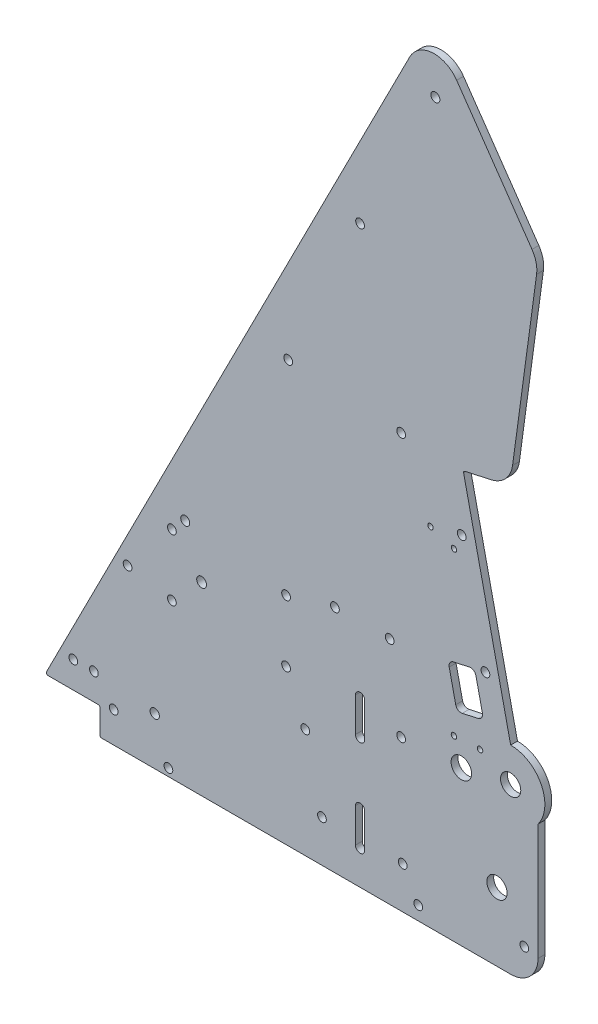
SolidWorks part; units mm, degrees
other "Markup1"
sketch "Sketch5"
ref_plane "Front Plane" through (0, 0, 0) normal (0, 0, 1) x (1, 0, 0)
ref_plane "Top Plane" through (0, 0, 0) normal (0, 1, 0) x (1, 0, 0)
ref_plane "Right Plane" through (0, 0, 0) normal (1, 0, 0) x (0, 0, -1)
sketch "Sketch1" plane through (0, 0, 0) normal (0, 0, 1) x (1, 0, 0)
  line L1 (228.6, -12.7) -> (228.6, 53.975)
  line L2 (178.7547, 351.4131) -> (0, 0)
  line L3 (228.6, 279.4) -> (178.7547, 351.4131)
  line L5 (0, 0) -> (25.4, 0)
  line L6 (25.4, 0) -> (25.4, -12.7)
  line L7 (25.4, -12.7) -> (228.6, -12.7)
  line L9 (215.9, 79.375) -> (193.9097, 178.5667)
  line L10 (193.9097, 178.5667) -> (215.6079, 183.377)
  line L11 (215.6079, 183.377) -> (228.6, 279.4)
  arc A0 (228.6, 53.975) -> (215.9, 79.375) centre (215.9, 63.5) ccw
  dimension "D7" = 12.7
  dimension "D8" = 76.2
  dimension "D10" = 31.75
  dimension "D2" = 292.1
  dimension "D3" = 25.4
  dimension "D4" = 215.9
  dimension "D5" = 394.2644
  dimension "D6" = 203.2
  dimension "D9" = 63.039
  dimension "D11" = 101.6
  dimension "D12" = 12.5
  dimension "D13" = 22.225
extrude "Boss-Extrude1" add sketch "Sketch1" along normal blind 3.175
sketch "Sketch2" plane through (0, 0, 3.175) normal (0, 0, 1) x (1, 0, 0)
  line L0 (178.7547, 351.4131) -> (0, 0) construction
  line L1 (25.4, -12.7) -> (228.6, -12.7) construction
  line L2 (215.9, 79.375) -> (193.9097, 178.5667) construction
  line L3 (193.9097, 178.5667) -> (215.6079, 183.377) construction
  line L4 (215.9, 79.375) -> (193.9097, 178.5667) construction
  line L5 (64.9432, 94.0578) -> (72.5445, 73.1732) construction
  line L6 (64.9432, 94.0578) -> (103.3734, 94.0578) construction
  line L10 (228.6, -12.7) -> (228.6, 53.975) construction
  circle A0 centre (64.9432, 94.0578) radius 2.0955
  circle A1 centre (180.975, 322.1643) radius 2.0955
  circle A2 centre (72.5445, 73.1732) radius 2.286
  circle A3 centre (193.2078, 152.3944) radius 2.032
  circle A4 centre (215.9, 63.5) radius 4.699
  circle A7 centre (173.0375, -6.35) radius 2.032
  circle A8 centre (204.203, 102.7985) radius 2.032
  circle A26 centre (209.55, 19.05) radius 4.699
  arc A30 (228.6, 53.975) -> (215.9, 79.375) centre (215.9, 63.5) ccw construction
  circle A31 centre (165.1, 179.3875) radius 2.032
  circle A35 centre (111.724, 87.4607) radius 2.032
  circle A36 centre (111.724, 58.8857) radius 2.032
  circle A37 centre (58.765, 58.8857) radius 2.032
  circle A38 centre (58.765, 87.4607) radius 2.032
  circle A39 centre (111.724, 58.8857) radius 1.905 construction
  circle A42 centre (111.724, 87.4607) radius 1.905 construction
  circle A43 centre (58.765, 58.8857) radius 1.905 construction
  circle A44 centre (58.765, 87.4607) radius 1.905 construction
  dimension "D3" = 4.191
  dimension "D5" = 4.191
  dimension "D9" = 4.572
  dimension "D20" = 9.398
  dimension "D23" = 9.398
  dimension "D18" = 4.064
  dimension "D26" = 4.064
  dimension "D14" = 4.064
  dimension "D10" = 4.064
  dimension "D2" = 15.24
  dimension "D6" = 15.24
  dimension "D7" = 22.225
  dimension "D21" = 44.45
  dimension "D22" = 6.35
  dimension "D19" = 160.3375
  dimension "D24" = 44.45
  dimension "D25" = 6.35
  dimension "D27" = 25.4
  dimension "D28" = 50.8
  dimension "D29" = 6.35
  dimension "D17" = 6.35
  dimension "D33" = 55.5625
  dimension "D15" = 114.3
  dimension "D4" = 180.975
  dimension "D8" = 70
extrude "Cut-Extrude1" cut sketch "Sketch2" against normal through all
sketch "Sketch7" plane through (0, 0, 3.175) normal (0, 0, 1) x (1, 0, 0)
  line L0 (146.05, 3.175) -> (146.05, 19.05) construction
  line L1 (143.891, 3.175) -> (143.891, 19.05)
  line L2 (148.209, 3.175) -> (148.209, 19.05)
  line L3 (146.05, 47.625) -> (146.05, 63.5) construction
  line L4 (143.891, 47.625) -> (143.891, 63.5)
  line L5 (148.209, 47.625) -> (148.209, 63.5)
  line L6 (25.4, -12.7) -> (228.6, -12.7) construction
  line L12 (228.6, -12.7) -> (228.6, 53.975) construction
  line L13 (25.4, -12.7) -> (228.6, -12.7) construction
  arc A0 (143.891, 3.175) -> (148.209, 3.175) centre (146.05, 3.175) ccw
  arc A1 (148.209, 19.05) -> (143.891, 19.05) centre (146.05, 19.05) ccw
  arc A2 (143.891, 47.625) -> (148.209, 47.625) centre (146.05, 47.625) ccw
  arc A3 (148.209, 63.5) -> (143.891, 63.5) centre (146.05, 63.5) ccw
  circle A8 centre (50.8, 9.525) radius 2.159
  point P2 (146.05, 11.1125)
  point P9 (146.05, 55.5625)
  dimension "D1" = 4.318
  dimension "D5" = 4.318
  dimension "D2" = 15.875
  dimension "D3" = 15.875
  dimension "D4" = 44.45
  dimension "D6" = 95.25
  dimension "D7" = 82.55
  dimension "D8" = 15.875
  dimension "D9" = 22.225
extrude "Cut-Extrude2" cut sketch "Sketch7" against normal through all
sketch "Sketch10" plane through (0, 0, 3.175) normal (0, 0, 1) x (1, 0, 0)
  circle A0 centre (120.65, 38.1) radius 2.032
  circle A1 centre (165.1, 57.15) radius 2.032
  circle A2 centre (13.0465, 12.3347) radius 2.032
  circle A3 centre (22.5715, 12.3347) radius 2.032
  circle A4 centre (38.2114, 62.6398) radius 2.032
  dimension "D1" = 4.064
  dimension "D3" = 38.1
  dimension "D2" = 120.65
  dimension "D4" = 63.5
  dimension "D5" = 69.85
extrude "Cut-Extrude3" cut sketch "Sketch10" against normal up to next
fillet "Fillet1" radius 12.7 4 edges at (228.6, -12.7, 1.5875) (178.7547, 351.4131, 1.5875) (215.6079, 183.377, 1.5875) (228.6, 279.4, 1.5875)
fillet "Fillet2" radius 0.7937 4 edges at (25.4, -12.7, 1.5875) (25.4, 0, 1.5875) (193.9097, 178.5667, 1.5875) (0, 0, 1.5875)
sketch "Sketch12" plane through (0, 0, 3.175) normal (0, 0, 1) x (1, 0, 0)
  circle A0 centre (31.75, 1.5875) radius 2.032
  circle A1 centre (173.0375, -6.35) radius 2.032
  circle A2 centre (222.25, 1.5875) radius 2.032
  circle A3 centre (57.15, -9.2075) radius 2.032
  circle A4 centre (57.15, -9.2075) radius 2.286 construction
  dimension "D1" = 4.064
  dimension "D2" = 4.064
extrude "Cut-Extrude5" cut sketch "Sketch12" against normal through all
sketch "Sketch13" plane through (0, 0, 3.175) normal (0, 0, 1) x (1, 0, 0)
  line L1 (228.6, 0) -> (228.6, 53.975) construction
  line L2 (1.2943, 0) -> (24.6062, 0) construction
  line L3 (26.1937, -12.7) -> (215.9, -12.7) construction
  circle A0 centre (112.7125, 182.5625) radius 2.032
  circle A1 centre (146.05, 254) radius 2.032
  dimension "D2" = 4.064
  dimension "D5" = 4.064
  dimension "D1" = 195.2625
  dimension "D3" = 82.55
  dimension "D4" = 254
  dimension "D6" = 115.8875
extrude "Cut-Extrude6" cut sketch "Sketch13" against normal through all
sketch "Sketch14" plane through (0, 0, 3.175) normal (0, 0, 1) x (1, 0, 0)
  line L5 (186.8444, 98.9502) -> (199.2434, 101.699)
  line L6 (186.8444, 98.9502) -> (190.9676, 80.3518)
  line L7 (190.9676, 80.3518) -> (203.3665, 83.1006)
  line L8 (199.2434, 101.699) -> (203.3665, 83.1006)
  line L14 (202.8168, 85.5804) -> (199.7931, 99.2192) construction
  line L15 (193.4474, 80.9015) -> (200.8868, 82.5508) construction
  line L16 (187.3942, 96.4704) -> (190.4178, 82.8316) construction
  line L17 (196.7636, 101.1493) -> (189.3242, 99.5) construction
  circle A0 centre (189.6022, 69.9806) radius 1.27
  circle A1 centre (201.7089, 70.5092) radius 1.27
  circle A2 centre (189.6022, 69.9806) radius 1.27 construction
  circle A3 centre (201.7089, 70.5092) radius 1.27 construction
  circle A4 centre (159.7935, 93.98) radius 2.032
  circle A5 centre (134.3935, 93.98) radius 2.032
  circle A6 centre (178.7216, 148.5324) radius 1.27
  circle A8 centre (178.7216, 148.5324) radius 1.27 construction
  circle A9 centre (189.6226, 145.0954) radius 1.27
  circle A10 centre (189.6226, 145.0954) radius 1.27 construction
  circle A11 centre (128.361, 6.6675) radius 2.032
  circle A12 centre (165.826, 6.6675) radius 2.032
  point P8 (152.4, 88.9)
  dimension "D1" = 4.064
extrude "Cut-Extrude7" cut sketch "Sketch14" against normal through all both and the other way through all
fillet "Fillet3" radius 2.54 4 edges at (199.2434, 101.699, 1.5875) (186.8444, 98.9502, 1.5875) (190.9676, 80.3518, 1.5875) (203.3665, 83.1006, 1.5875)
sketch "Sketch15" plane through (0, 0, 3.175) normal (0, 0, 1) x (1, 0, 0)
  circle A0 centre (193.04, 58.801) radius 4.7625 construction
  circle A1 centre (193.04, 58.801) radius 4.7625
extrude "Cut-Extrude8" cut sketch "Sketch15" against normal through all
equation "\"D6@Sketch2\"=\"D2@Sketch2\""
